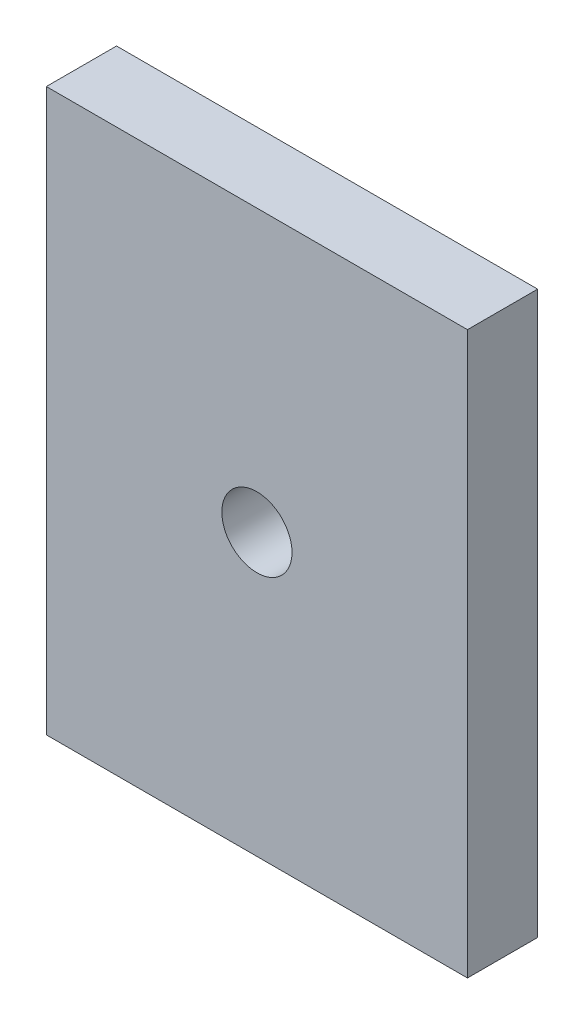
SolidWorks part; units mm, degrees
material "Acrylic (Medium-high impact)"
ref_plane "Front Plane" through (0, 0, 0) normal (0, 0, 1) x (1, 0, 0)
ref_plane "Top Plane" through (0, 0, 0) normal (0, 1, 0) x (1, 0, 0)
ref_plane "Right Plane" through (0, 0, 0) normal (1, 0, 0) x (0, 0, -1)
sketch "Sketch1" plane through (0, 0, 0) normal (0, 0, 1) x (1, 0, 0)
  line L1 (-38.1, 50.8) -> (38.1, 50.8)
  line L2 (-38.1, 50.8) -> (-38.1, -50.8)
  line L3 (-38.1, -50.8) -> (38.1, -50.8)
  line L4 (38.1, 50.8) -> (38.1, -50.8)
  line L5 (-38.1, 50.8) -> (38.1, -50.8) construction
  line L6 (-38.1, -50.8) -> (38.1, 50.8) construction
  point P0 (0, 0)
  dimension "D1" = 76.2
  dimension "D2" = 101.6
extrude "Boss-Extrude1" add sketch "Sketch1" along normal blind 12.7
sketch "Sketch2" plane through (0, 0, 12.7) normal (0, 0, 1) x (1, 0, 0)
  circle A0 centre (0, 0) radius 6.35
  dimension "D1" = 12.7
extrude "Cut-Extrude1" cut sketch "Sketch2" against normal through all
